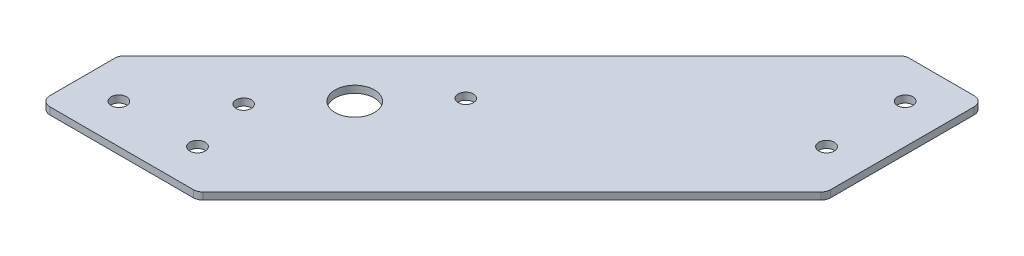
SolidWorks part; units mm, degrees
ref_plane "Front Plane" through (0, 0, 0) normal (0, 0, 1) x (1, 0, 0)
ref_plane "Top Plane" through (0, 0, 0) normal (0, 1, 0) x (1, 0, 0)
ref_plane "Right Plane" through (0, 0, 0) normal (1, 0, 0) x (0, 0, -1)
sketch "Sketch1" plane through (0, 0, 0) normal (0, 1, 0) x (1, 0, 0)
  line L0 (0, 0) -> (0, 152.4)
  line L1 (0, 152.4) -> (-25.4, 152.4)
  line L2 (-25.4, 152.4) -> (-152.4, 25.4)
  line L3 (-152.4, 25.4) -> (-152.4, 0)
  line L4 (-152.4, 0) -> (0, 0)
  circle A0 centre (-12.7, 12.7) radius 2.4892
  circle A1 centre (-38.1, 12.7) radius 2.4892
  circle A2 centre (-63.5, 12.7) radius 2.4892
  circle A3 centre (-88.9, 12.7) radius 2.4892
  circle A4 centre (-114.3, 12.7) radius 2.4892
  circle A5 centre (-12.7, 38.1) radius 2.4892
  circle A6 centre (-12.7, 63.5) radius 2.4892
  circle A7 centre (-12.7, 88.9) radius 2.4892
  circle A8 centre (-12.7, 114.3) radius 2.4892
  circle A9 centre (-139.7, 12.7) radius 2.4892
  circle A13 centre (-12.7, 139.7) radius 2.4892
  circle A17 centre (-101.6, 50.8) radius 6.35
  dimension "D4" = 12.7
  dimension "D5" = 12.7
  dimension "D8" = 12.7
  dimension "D1" = 152.4
  dimension "D2" = 25.4
  dimension "D3" = 152.4
  dimension "D9" = 101.6
  dimension "D10" = 50.8
  dimension "D11" = 25.4
  dimension "D6" = 6
  dimension "D7" = 6
extrude "Boss-Extrude2" add sketch "Sketch1" along normal mid plane 2.286
sketch "Sketch2" plane through (0, 1.143, 0) normal (0, 1, 0) x (1, 0, 0)
  line L0 (0, 0) -> (0, 101.6)
  line L1 (0, 0) -> (0, 152.4) construction
  line L2 (0, 101.6) -> (-101.6, 0)
  line L3 (-152.4, 0) -> (0, 0) construction
  line L4 (-101.6, 0) -> (0, 0)
  dimension "D1" = 45
  dimension "D2" = 101.6
  dimension "D3" = 101.6
extrude "Cut-Extrude1" cut sketch "Sketch2" against normal through all
sketch "Sketch3" plane through (0, 1.143, 0) normal (0, 1, 0) x (1, 0, 0)
  line L0 (-101.6, 0) -> (-101.6, 15.1204)
  line L1 (-101.6, 15.1204) -> (-15.6123, 101.1081)
  line L2 (-15.6123, 101.1081) -> (0, 101.6)
  line L3 (0, 101.6) -> (-101.6, 0)
extrude "Boss-Extrude3" add sketch "Sketch3" against normal blind 2.286
fillet "Fillet3" radius 3.175 6 edges at (-152.4, 0, 0) (-25.4, 0, -152.4) (0, 0, -152.4) (0, 0, -101.6) (-101.6, 0, 0) (-152.4, 0, -25.4)
ref_plane "Plane1" through (-152.4, 1.143, -24.0849) normal (0, 0, 1) x (1, 0, 0)
sketch "Sketch5" plane through (0, 1.143, 0) normal (0, 1, 0) x (1, 0, 0)
  line L0 (0, 0) -> (0, 152.4) construction
  line L1 (0, 152.4) -> (-152.4, 152.4) construction
  line L2 (0, 0) -> (-152.4, 0) construction
  line L3 (-152.4, 0) -> (-152.4, 152.4) construction
  dimension "D1" = 152.4
  dimension "D2" = 152.4
hole_wizard "#10 (0.1935) Diameter Hole1" positions "Sketch7" profile "Sketch6" hole size "#10" standard "ANSI Inch" end condition through all
sketch "Sketch7" plane through (0, 1.143, 0) normal (0, 1, 0) x (1, 0, 0)
  line L0 (-118.7264, 32.0425) -> (-84.4736, 69.5575) construction
  circle A0 centre (-101.6, 50.8) radius 6.35 construction
  point P0 (-118.7264, 32.0425)
  point P2 (-84.4736, 69.5575)
  point P10 (-101.6, 50.8)
  dimension "D1" = 50.8
sketch "Sketch6" plane through (-118.7264, 1.143, -32.0425) normal (1, 0, 0) x (0, 0, 1)
  line L0 (0, 0) -> (0, 2.286)
  line L1 (0, 2.286) -> (2.4574, 2.286)
  line L2 (2.4574, 2.286) -> (2.4574, 0)
  line L5 (2.4574, 0) -> (0, 0)
  line L11 (0, -6.35) -> (0, 107.95) construction
  dimension "Thru Hole Dia." = 4.9149
  dimension "Thru Hole Depth" = 2.286
equation "\"0.09inin\"=0.1"
